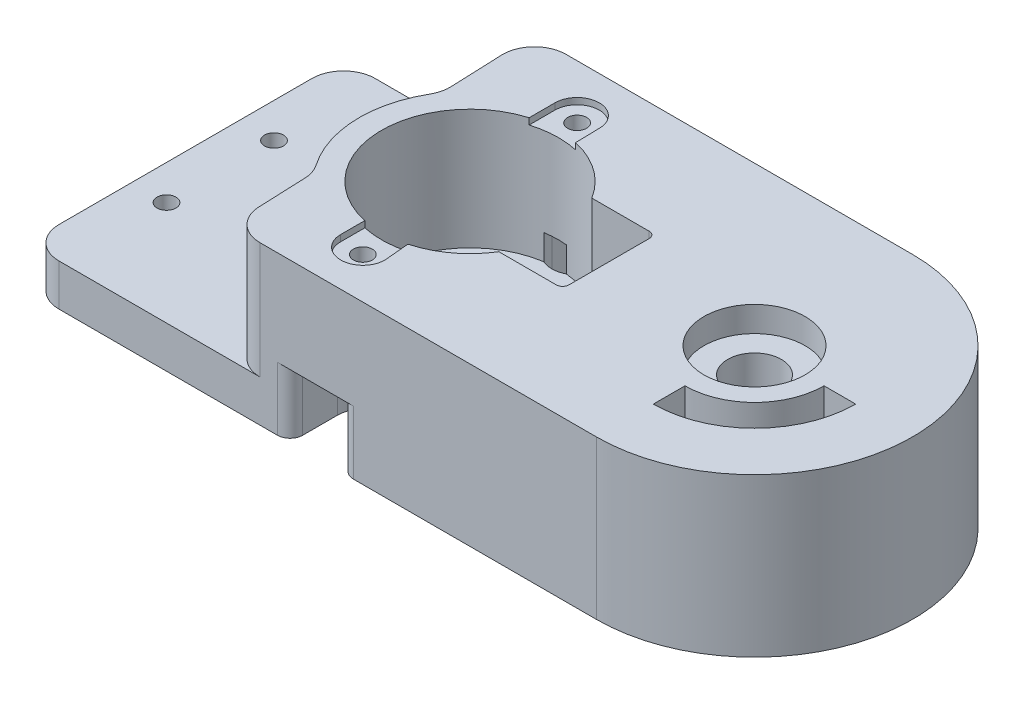
SolidWorks part; units mm, degrees
ref_plane "Front Plane" through (0, 0, 0) normal (0, 0, 1) x (1, 0, 0)
ref_plane "Top Plane" through (0, 0, 0) normal (0, 1, 0) x (1, 0, 0)
ref_plane "Right Plane" through (0, 0, 0) normal (1, 0, 0) x (0, 0, -1)
sketch "Sketch1" plane through (0, 0, 0) normal (0, 1, 0) x (1, 0, 0)
  line L1 (-45, 25) -> (45, 25)
  line L2 (-45, 25) -> (-45, -25)
  line L3 (-45, -25) -> (45, -25)
  line L5 (-45, 25) -> (45, -25) construction
  line L6 (-45, -25) -> (45, 25) construction
  arc A0 (45, 25) -> (45, -25) centre (45, 0) cw
  point P0 (0, 0)
  dimension "D1" = 50
  dimension "D2" = 90
extrude "Boss-Extrude1" add sketch "Sketch1" along normal blind 25
sketch "Sketch2" plane through (0, 25, 0) normal (0, 1, 0) x (1, 0, 0)
  circle A0 centre (0, 0) radius 14
extrude "Cut-Extrude1" cut sketch "Sketch2" against normal blind 19
sketch "Sketch3" plane through (0, 25, 0) normal (0, 1, 0) x (1, 0, 0)
  line L0 (-0.5462, 17.4915) -> (0.5462, -17.4915) construction
  line L1 (-4.0462, 17.4915) -> (-4.0462, 13.4026)
  line L2 (2.9538, 17.4915) -> (3.0352, 13.667)
  line L3 (-2.9538, -17.4915) -> (-2.9538, -13.6848)
  line L4 (4.0462, -17.4915) -> (3.6861, -13.506)
  arc A0 (2.9538, 17.4915) -> (-4.0462, 17.4915) centre (-0.5462, 17.4915) ccw
  circle A1 centre (0, 0) radius 14 construction
  arc A2 (-4.0462, 13.4026) -> (3.0472, 13.6644) centre (0, 0) cw
  arc A3 (4.0462, -17.4915) -> (-2.9538, -17.4915) centre (0.5462, -17.4915) cw
  arc A4 (-2.9538, -13.6848) -> (3.6861, -13.506) centre (0, 0) ccw
  point P4 (0, 0)
extrude "Cut-Extrude2" cut sketch "Sketch3" against normal blind 1
sketch "Sketch4" plane through (0, 24, 0) normal (0, 1, 0) x (1, 0, 0)
  circle A0 centre (-0.5462, 17.4915) radius 1.5
extrude "Cut-Extrude3" cut sketch "Sketch4" against normal through all
sketch "Sketch5" plane through (0, 24, 0) normal (0, 1, 0) x (1, 0, 0)
  circle A0 centre (0.5462, -17.4915) radius 1.5
extrude "Cut-Extrude4" cut sketch "Sketch5" against normal through all
sketch "Sketch6" plane through (0, 25, 0) normal (0, 1, 0) x (1, 0, 0)
  line L0 (22, 7.35) -> (22, -7.35)
  line L1 (22, 7.35) -> (11.9154, 7.35)
  line L2 (22, -7.35) -> (11.9154, -7.35)
  line L3 (11.9203, -7.3421) -> (11.9154, -7.35)
  arc A0 (3.6861, -13.506) -> (3.0352, 13.667) centre (0, 0) ccw construction
  circle A1 centre (0, 0) radius 14 construction
  arc A2 (11.9154, 7.35) -> (11.9203, -7.3421) centre (0, 0) cw
  point P3 (22, 0)
  dimension "D1" = 22
  dimension "D2" = 14.7
extrude "Cut-Extrude7" cut sketch "Sketch6" against normal blind 19
fillet "Fillet1" radius 1 2 edges at (22, 15.5, 7.35) (22, 15.5, -7.35)
sketch "Sketch7" plane through (0, 25, 0) normal (0, 1, 0) x (1, 0, 0)
  line L0 (-14.4117, 9.9274) -> (-15.0195, 25)
  line L2 (-13.5656, -11.0556) -> (-13.0032, -25)
  line L3 (-45, -25) -> (45, -25) construction
  line L4 (45, 25) -> (-45, 25) construction
  line L5 (-15.0195, 25) -> (-45, 25)
  line L6 (-45, 25) -> (-45, -25)
  line L7 (-45, -25) -> (-13.0032, -25)
  arc A0 (-14.4117, 9.9274) -> (-13.5656, -11.0556) centre (0, 0) ccw
extrude "Cut-Extrude8" cut sketch "Sketch7" against normal blind 18.4
fillet "Fillet2" radius 5 6 edges at (-45, 3.3, -25) (-45, 3.3, 25) (-14.4117, 15.8, -9.9274) (-13.5656, 15.8, 11.0556) (-15.0195, 15.8, -25) (-13.0032, 15.8, 25)
sketch "Sketch8" plane through (0, 6.6, 0) normal (0, 1, 0) x (1, 0, 0)
  line L0 (-39.5, 8.5) -> (-39.5, -8.5) construction
  line L1 (-45, 20) -> (-45, -20) construction
  circle A0 centre (-39.5, 8.5) radius 1.5
  circle A1 centre (-39.5, -8.5) radius 1.5
  point P3 (-39.5, 0)
  dimension "D1" = 5.5
extrude "Cut-Extrude9" cut sketch "Sketch8" against normal through all
sketch "Sketch9" plane through (0, 0, 0) normal (0, -1, 0) x (1, 0, 0)
  circle A0 centre (-39.5, 8.5) radius 2.5
  circle A1 centre (-39.5, -8.5) radius 2.5
extrude "Cut-Extrude10" cut sketch "Sketch9" against normal blind 2
fillet "Fillet3" radius 2 2 edges at (-39.5, 0, -11) (-39.5, 0, 6)
sketch "Sketch10" plane through (0, 0, 0) normal (0, -1, 0) x (1, 0, 0)
  line L0 (-3.4538, 17.4915) -> (-3.4538, 25)
  line L1 (-40, 25) -> (45, 25) construction
  line L2 (-3.4538, 25) -> (4.5462, 25)
  line L3 (4.5462, 25) -> (4.5462, 17.4915)
  line L4 (-4.5462, -17.4915) -> (-4.5462, -25)
  line L5 (45, -25) -> (-40, -25) construction
  line L6 (-4.5462, -25) -> (3.4538, -25)
  line L7 (3.4538, -25) -> (3.4538, -17.4915)
  arc A0 (-3.4538, 17.4915) -> (4.5462, 17.4915) centre (0.5462, 17.4915) ccw
  arc A1 (3.4538, -17.4915) -> (-4.5462, -17.4915) centre (-0.5462, -17.4915) ccw
extrude "Cut-Extrude11" cut sketch "Sketch10" against normal blind 10
fillet "Fillet4" radius 2 4 edges at (3.4538, 5, -25) (-4.5462, 5, -25) (4.5462, 5, 25) (-3.4538, 5, 25)
sketch "Sketch11" plane through (0, 25, 0) normal (0, 1, 0) x (1, 0, 0)
  circle A0 centre (45, 0) radius 8
extrude "Cut-Extrude12" cut sketch "Sketch11" against normal blind 4
sketch "Sketch12" plane through (0, 21, 0) normal (0, 1, 0) x (1, 0, 0)
  circle A0 centre (45, 0) radius 4.25
extrude "Cut-Extrude13" cut sketch "Sketch12" against normal through all
sketch "Sketch19" plane through (0, 0, 0) normal (0, -1, 0) x (1, 0, 0)
  line L0 (45, 11) -> (45, 16)
  line L1 (56, 0) -> (61, 0)
  arc A0 (45, 11) -> (56, 0) centre (45, 0) cw
  arc A1 (45, 16) -> (61, 0) centre (45, 0) cw
extrude "Cut-Extrude16" cut sketch "Sketch19" against normal blind 25
